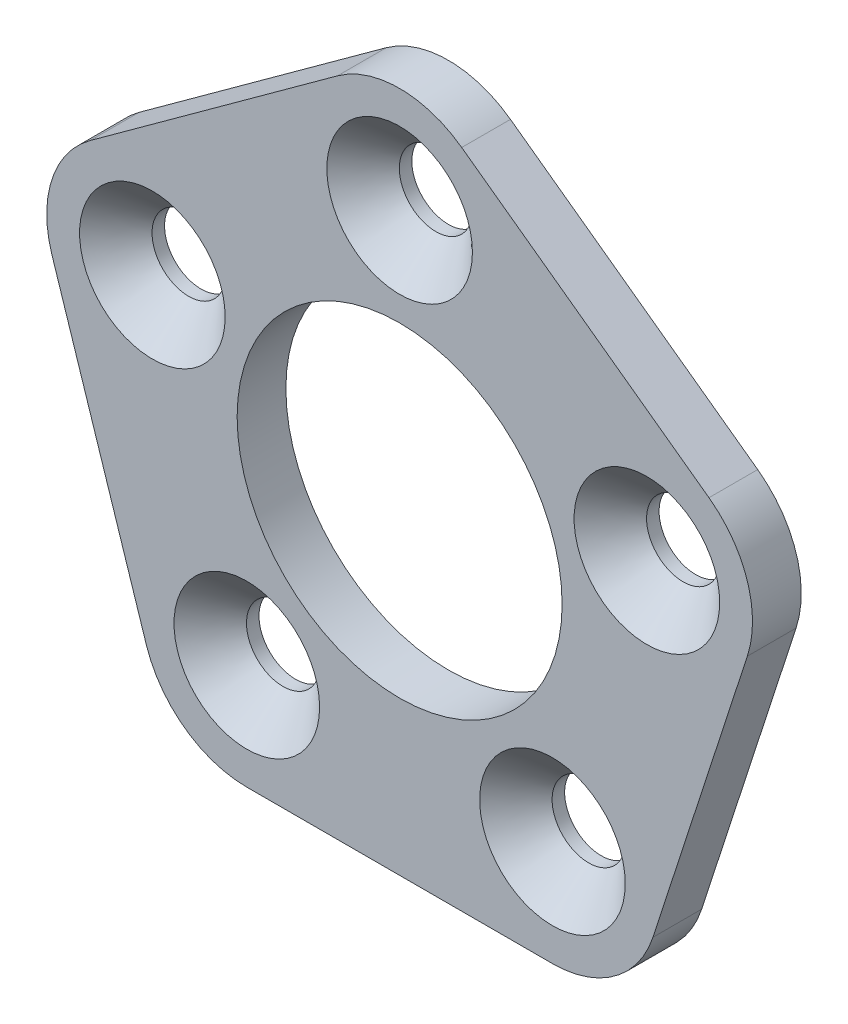
SolidWorks part; units mm, degrees
material "AISI Type A2 Tool Steel"
ref_plane "Front" through (0, 0, 0) normal (0, 0, 1) x (1, 0, 0)
ref_plane "Top" through (0, 0, 0) normal (0, 1, 0) x (1, 0, 0)
ref_plane "Right" through (0, 0, 0) normal (1, 0, 0) x (0, 0, -1)
sketch "Sketch1" plane through (0, 0, 0) normal (0, 0, 1) x (1, 0, 0)
  line L0 (-21.3988, 2.9357) -> (-15.5864, -14.9529)
  line L1 (-19.0375, 10.2029) -> (-3.8206, 21.2586)
  line L2 (-9.4046, -19.4443) -> (9.4046, -19.4443)
  line L3 (15.5864, -14.9529) -> (21.3988, 2.9357)
  line L4 (3.8206, 21.2586) -> (19.0375, 10.2029)
  circle A0 centre (0, 0) radius 16 construction
  circle A1 centre (0, 0) radius 19 construction
  circle A2 centre (0, 0) radius 10
  arc A3 (3.8206, 21.2586) -> (-3.8206, 21.2586) centre (0, 16) ccw
  arc A4 (21.3988, 2.9357) -> (19.0375, 10.2029) centre (15.2169, 4.9443) ccw
  arc A5 (9.4046, -19.4443) -> (15.5864, -14.9529) centre (9.4046, -12.9443) ccw
  arc A6 (-15.5864, -14.9529) -> (-9.4046, -19.4443) centre (-9.4046, -12.9443) ccw
  arc A7 (-19.0375, 10.2029) -> (-21.3988, 2.9357) centre (-15.2169, 4.9443) ccw
  arc A8 (-6.3645, 14.6797) -> (6.3645, 14.6797) centre (0, 16) ccw construction
  arc A9 (-15.9279, -1.5167) -> (-11.9945, 10.5893) centre (-15.2169, 4.9443) ccw construction
  arc A10 (-3.4795, -15.6171) -> (-13.7775, -8.1352) centre (-9.4046, -12.9443) ccw construction
  arc A11 (13.7775, -8.1352) -> (3.4795, -15.6171) centre (9.4046, -12.9443) ccw construction
  arc A12 (15.9279, -1.5167) -> (18.9969, -0.3436) centre (15.2169, 4.9443) ccw construction
  arc A13 (15.1668, 11.4441) -> (11.9945, 10.5893) centre (15.2169, 4.9443) ccw construction
  arc A14 (11.9945, 10.5893) -> (15.9279, -1.5167) centre (15.2169, 4.9443) ccw construction
  arc A15 (6.3645, 14.6797) -> (6.1972, 17.9609) centre (0, 16) ccw construction
  arc A16 (-6.1972, 17.9609) -> (-6.3645, 14.6797) centre (0, 16) ccw construction
  arc A17 (-3.8206, 21.2586) -> (-6.1972, 17.9609) centre (0, 16) ccw construction
  arc A18 (6.1972, 17.9609) -> (3.8206, 21.2586) centre (0, 16) ccw construction
  arc A19 (-11.9945, 10.5893) -> (-15.1668, 11.4441) centre (-15.2169, 4.9443) ccw construction
  arc A20 (-15.1668, 11.4441) -> (-19.0375, 10.2029) centre (-15.2169, 4.9443) ccw construction
  arc A21 (-21.3988, 2.9357) -> (-18.9969, -0.3436) centre (-15.2169, 4.9443) ccw construction
  arc A22 (-18.9969, -0.3436) -> (-15.9279, -1.5167) centre (-15.2169, 4.9443) ccw construction
  arc A23 (-13.7775, -8.1352) -> (-15.5708, -10.8881) centre (-9.4046, -12.9443) ccw construction
  arc A24 (-15.5708, -10.8881) -> (-15.5864, -14.9529) centre (-9.4046, -12.9443) ccw construction
  arc A25 (-5.5436, -18.1733) -> (-3.4795, -15.6171) centre (-9.4046, -12.9443) ccw construction
  arc A26 (-9.4046, -19.4443) -> (-5.5436, -18.1733) centre (-9.4046, -12.9443) ccw construction
  arc A27 (3.4795, -15.6171) -> (5.5436, -18.1733) centre (9.4046, -12.9443) ccw construction
  arc A28 (5.5436, -18.1733) -> (9.4046, -19.4443) centre (9.4046, -12.9443) ccw construction
  arc A29 (15.5864, -14.9529) -> (15.5708, -10.8881) centre (9.4046, -12.9443) ccw construction
  arc A30 (15.5708, -10.8881) -> (13.7775, -8.1352) centre (9.4046, -12.9443) ccw construction
  arc A31 (19.0375, 10.2029) -> (15.1668, 11.4441) centre (15.2169, 4.9443) ccw construction
  arc A32 (18.9969, -0.3436) -> (21.3988, 2.9357) centre (15.2169, 4.9443) ccw construction
  point P17 (0, 0)
  dimension "D1" = 32
  dimension "D2" = 38
  dimension "D3" = 20
  dimension "D4" = 13
  dimension "D5" = 5
extrude "Boss-Extrude1" add sketch "Sketch1" against normal blind 3
hole_wizard "CSK for M4 SFHCS1" positions "Sketch2" profile "Sketch4" countersink size "M4" standard "ANSI Metric"
sketch "Sketch2" plane through (0, 0, 0) normal (0, 0, 1) x (1, 0, 0)
  circle A0 centre (0, 0) radius 16 construction
  point P2 (0, 16)
  point P17 (15.2169, 4.9443)
  point P18 (9.4046, -12.9443)
  point P19 (-9.4046, -12.9443)
  point P20 (-15.2169, 4.9443)
  point P22 (14.7865, 6.1122)
  point P23 (8.7245, -13.4121)
  point P24 (0, 16)
  point P25 (0, 0)
  dimension "D1" = 5
sketch "Sketch4" plane through (0, 16, 0) normal (1, 0, 0) x (0, -1, 0)
  line L0 (0, 0) -> (0, 6.4519)
  line L1 (0, 6.4519) -> (2.25, 5.1)
  line L2 (2.25, 5.1) -> (2.25, 2.23)
  line L3 (2.25, 2.23) -> (4.48, 0)
  line L5 (4.48, 0) -> (0, 0)
  line L6 (-2.25, 2.23) -> (-4.48, 0) construction
  line L10 (0, 6.4519) -> (-2.25, 5.1) construction
  line L11 (0, -6.35) -> (0, 107.95) construction
  dimension "Hole Dia." = 4.5
  dimension "Hole Depth" = 5.1
  dimension "Near C'Sink Dia." = 8.96
  dimension "Near C'Sink Angle" = 90
  dimension "Drill Angle" = 118
